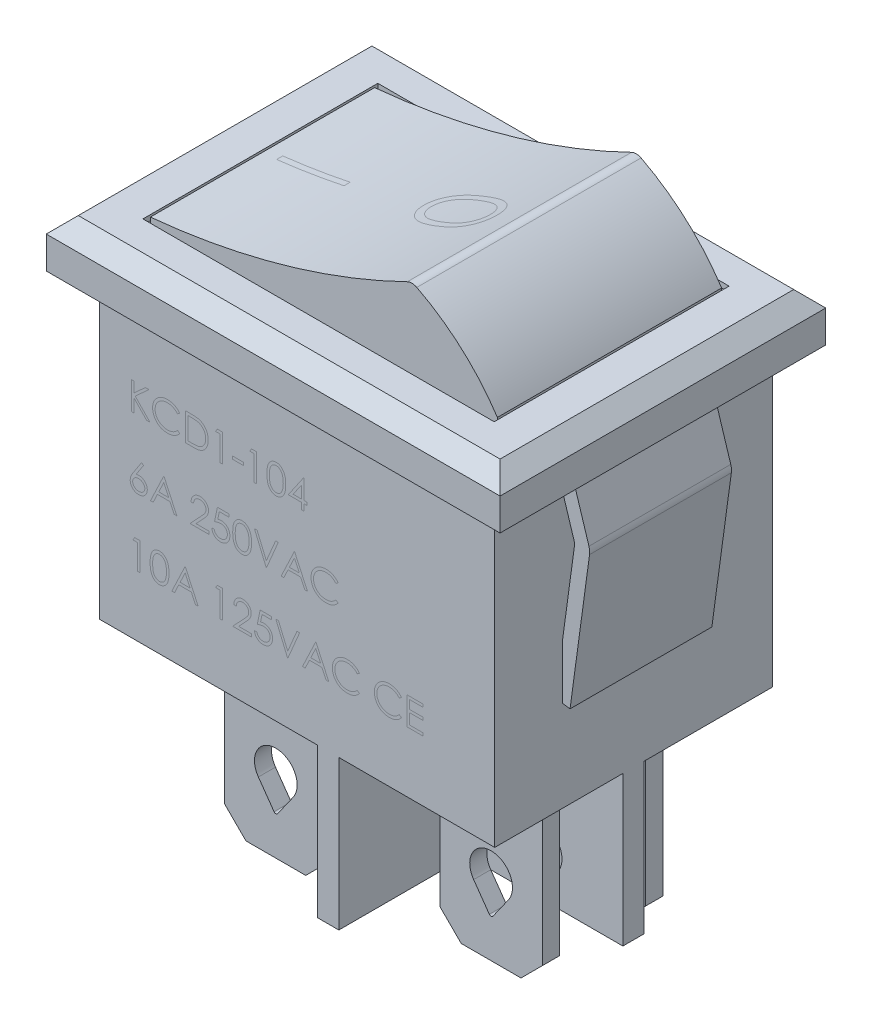
SolidWorks part; units mm, degrees
ref_plane "Front Plane" through (0, 0, 0) normal (0, 0, 1) x (1, 0, 0)
ref_plane "Top Plane" through (0, 0, 0) normal (0, 1, 0) x (1, 0, 0)
ref_plane "Right Plane" through (0, 0, 0) normal (1, 0, 0) x (0, 0, -1)
sketch "Sketch1" plane through (0, 0, 0) normal (0, 0, 1) x (1, 0, 0)
  line L1 (9.25, 7) -> (-9.25, 7)
  line L2 (9.25, 7) -> (9.25, -7)
  line L3 (9.25, -7) -> (-9.25, -7)
  line L4 (-9.25, 7) -> (-9.25, -7)
  line L5 (9.25, 7) -> (-9.25, -7) construction
  line L6 (9.25, -7) -> (-9.25, 7) construction
  point P0 (0, 0)
  dimension "D1" = 14
  dimension "D2" = 18.5
extrude "Boss-Extrude1" add sketch "Sketch1" along normal mid plane 13
sketch "Sketch2" plane through (0, 7, 0) normal (0, 1, 0) x (1, 0, 0)
  line L1 (10.625, 7.625) -> (-10.625, 7.625)
  line L2 (10.625, 7.625) -> (10.625, -7.625)
  line L3 (10.625, -7.625) -> (-10.625, -7.625)
  line L4 (-10.625, 7.625) -> (-10.625, -7.625)
  line L5 (10.625, 7.625) -> (-10.625, -7.625) construction
  line L6 (10.625, -7.625) -> (-10.625, 7.625) construction
  point P0 (0, 0)
  dimension "D1" = 15.25
  dimension "D2" = 21.25
extrude "Boss-Extrude2" add sketch "Sketch2" along normal blind 2.25
chamfer "Chamfer1" distance 0.75 angle 45 4 edges at (0, 9.25, -7.625) (10.625, 9.25, 0) (0, 9.25, 7.625) (-10.625, 9.25, 0)
sketch "Sketch11" plane through (0, 9.25, 0) normal (0, 1, 0) x (1, 0, 0)
  line L0 (-10.625, -7.625) -> (-10.625, 7.625) construction
  line L1 (-8.225, -5.5) -> (8.225, -5.5)
  line L2 (-8.225, -5.5) -> (-8.225, 5.5)
  line L3 (-8.225, 5.5) -> (8.225, 5.5)
  line L4 (8.225, -5.5) -> (8.225, 5.5)
  line L5 (-8.225, -5.5) -> (8.225, 5.5) construction
  line L6 (-8.225, 5.5) -> (8.225, -5.5) construction
  point P0 (0, 0)
  dimension "D1" = 2.4
  dimension "D2" = 11
extrude "Cut-Extrude6" cut sketch "Sketch11" against normal blind 0.25
sketch "Sketch3" plane through (0, 0, 0) normal (0, 0, 1) x (1, 0, 0)
  line L0 (8.125, 9.25) -> (4.125, 12.75) construction
  line L1 (-9.875, 9.25) -> (9.875, 9.25) construction
  line L2 (10.625, 8.5) -> (10.625, 7) construction
  line L4 (-10.625, 8.5) -> (-10.625, 7) construction
  line L5 (-8.125, 9.25) -> (8.125, 9.25) construction
  line L6 (-8.125, 9.25) -> (8.125, 9.25) construction
  line L7 (-8.125, 9.25) -> (-8.125, 8.95)
  line L8 (-8.125, 8.95) -> (8.125, 8.95)
  line L9 (8.125, 9.25) -> (8.125, 8.95)
  arc A0 (-8.125, 9.25) -> (3.9043, 12.6413) centre (-11.4546, 44.0913) ccw
  arc A1 (4.3525, 12.6366) -> (8.125, 9.25) centre (-0.2233, 3.7449) cw
  arc A2 (3.9043, 12.6413) -> (4.3525, 12.6366) centre (4.1237, 12.192) cw
  point P6 (-8.125, 9.25)
  dimension "D4" = 35
  dimension "D5" = 6.5
  dimension "D6" = 10
  dimension "D7" = 0.5
  dimension "D1" = 2.5
  dimension "D2" = 3.5
  dimension "D3" = 2.5
  dimension "D8" = 0.3
extrude "Boss-Extrude3" add sketch "Sketch3" along normal mid plane 10.5
sketch "Sketch4" plane through (0, -7, 0) normal (0, -1, 0) x (-1, 0, 0)
  line L0 (-9.25, 6.5) -> (9.25, 6.5) construction
  line L1 (-1.95, 6.5) -> (-0.95, 6.5)
  line L2 (-1.95, 6.5) -> (-1.95, -6.5)
  line L3 (-1.95, -6.5) -> (-0.95, -6.5)
  line L4 (-0.95, 6.5) -> (-0.95, -6.5)
  line L5 (9.25, -6.5) -> (-9.25, -6.5) construction
  line L6 (-9.25, -6.5) -> (-9.25, 6.5) construction
  line L7 (-1.45, -6.5) -> (-1.45, 6.5) construction
  line L8 (-9.25, 0.5) -> (9.25, 0.5)
  line L9 (-9.25, 0.5) -> (-9.25, -0.5)
  line L10 (-9.25, -0.5) -> (9.25, -0.5)
  line L11 (9.25, 0.5) -> (9.25, -0.5)
  line L12 (-9.25, 0.5) -> (9.25, -0.5) construction
  line L13 (-9.25, -0.5) -> (9.25, 0.5) construction
  line L14 (9.25, -6.5) -> (9.25, 6.5) construction
  line L15 (0, 0) -> (4.2269, 0) construction
  line M5 (9.25, 6.5) -> (-9.25, 6.5)
  line M6 (-9.25, 6.5) -> (-9.25, -6.5)
  line M7 (-9.25, -6.5) -> (9.25, -6.5)
  line M8 (9.25, -6.5) -> (9.25, 6.5)
  dimension "D1" = 8.3
  dimension "D2" = 1
extrude "Boss-Extrude4" add sketch "Sketch4" along normal blind 7 contours L10 L2 L8 M6 | L4 L10 L8 M8 | L2 L10 L4 L8 | L2 L8 L4 M5 | L10 L2 L4 M7 region at (1.45, -7, -3.5) region at (1.45, -7, 0) region at (5.6, -7, 0) region at (-4.15, -7, 0) region at (1.45, -7, 3.5)
sketch "Sketch5" plane through (0, -7, 0) normal (0, -1, 0) x (1, 0, 0)
  line L0 (1.95, 6.5) -> (9.25, 6.5) construction
  line L1 (3, 2.82) -> (7.8, 2.82)
  line L2 (3, 2.82) -> (3, 2.02)
  line L3 (3, 2.02) -> (7.8, 2.02)
  line L4 (7.8, 2.82) -> (7.8, 2.02)
  line L5 (3, 2.82) -> (7.8, 2.02) construction
  line L6 (3, 2.02) -> (7.8, 2.82) construction
  line L7 (-6.2, -2.9) -> (-1.4, -2.9)
  line L8 (-6.2, -2.9) -> (-6.2, -3.7)
  line L9 (-6.2, -3.7) -> (-1.4, -3.7)
  line L10 (-1.4, -2.9) -> (-1.4, -3.7)
  line L11 (-6.2, -2.9) -> (-1.4, -3.7) construction
  line L12 (-6.2, -3.7) -> (-1.4, -2.9) construction
  line L13 (-9.25, -6.5) -> (0.95, -6.5) construction
  line L14 (9.25, 6.5) -> (9.25, -6.5) construction
  line L15 (0, 0) -> (-13.591, 0) construction
  line L16 (0, 0) -> (0, 9.8331) construction
  line L17 (3, -2.02) -> (7.8, -2.82) construction
  line L18 (3, -2.82) -> (7.8, -2.02) construction
  line L19 (7.8, -2.82) -> (7.8, -2.02)
  line L20 (3, -2.02) -> (7.8, -2.02)
  line L21 (3, -2.82) -> (3, -2.02)
  line L22 (3, -2.82) -> (7.8, -2.82)
  line L23 (-6.2, 3.7) -> (-1.4, 2.9) construction
  line L24 (-6.2, 2.9) -> (-1.4, 3.7) construction
  line L25 (-1.4, 2.9) -> (-1.4, 3.7)
  line L26 (-6.2, 3.7) -> (-1.4, 3.7)
  line L27 (-6.2, 2.9) -> (-6.2, 3.7)
  line L28 (-6.2, 2.9) -> (-1.4, 2.9)
  point P0 (5.4, 2.42)
  point P5 (-3.8, -3.3)
  point P24 (5.4, -2.42)
  point P29 (-3.8, 3.3)
  dimension "D1" = 4.8
  dimension "D2" = 0.8
  dimension "D3" = 14
  dimension "D4" = 3.68
  dimension "D5" = 2.8
  dimension "D6" = 1.45
extrude "Boss-Extrude5" add sketch "Sketch5" along normal blind 8.36
chamfer "Chamfer2" distance 1 angle 45 8 edges at (7.8, -15.36, 2.42) (3, -15.36, 2.42) (-1.4, -15.36, -3.3) (-6.2, -15.36, -3.3) (7.8, -15.36, -2.42) (3, -15.36, -2.42) (-1.4, -15.36, 3.3) (-6.2, -15.36, 3.3)
sketch "Sketch6" plane through (0, 0, 2.82) normal (0, 0, 1) x (1, 0, 0)
  line L0 (6.8, -15.36) -> (4, -15.36) construction
  line L1 (5.3183, -13.5177) -> (4.5832, -12.4769)
  line L2 (5.4, -11.9) -> (5.4, -15.36) construction
  line L3 (-1.4, -10.68) -> (3, -10.68) construction
  line L4 (5.4817, -13.5177) -> (6.2168, -12.4769)
  line L5 (-1.4, -14.36) -> (-1.4, -7) construction
  line L6 (3, -14.36) -> (3, -7) construction
  line L7 (0.8, -10.68) -> (0.8, -14.52) construction
  line L9 (-3.8817, -13.5177) -> (-4.6168, -12.4769)
  line L10 (-3.7183, -13.5177) -> (-2.9832, -12.4769)
  arc A0 (6.2168, -12.4769) -> (4.5832, -12.4769) centre (5.4, -11.9) ccw
  arc A1 (5.4817, -13.5177) -> (5.3183, -13.5177) centre (5.4, -13.46) cw
  arc A2 (-3.8817, -13.5177) -> (-3.7183, -13.5177) centre (-3.8, -13.46) ccw
  arc A3 (-4.6168, -12.4769) -> (-2.9832, -12.4769) centre (-3.8, -11.9) cw
  dimension "D1" = 0.1
  dimension "D2" = 2.66
  dimension "D3" = 1
  dimension "D4" = 1.8
extrude "Cut-Extrude1" cut sketch "Sketch6" against normal through all and the other way through all
ref_plane "Plane2" through (-3.0139, 10.6909, 0) normal (0.2713, -0.9625, 0) x (-0.9625, -0.2713, 0)
sketch "Sketch7" plane through (-3.0139, 10.6909, 0) normal (0.2713, -0.9625, 0) x (-0.9625, -0.2713, 0)
  text T0 "<r90>I</r>" font "Century Gothic" height 3.2
  text T1 "<r90>0</r>"
wrap "Wrap1" sketch "Sketch7" wrap type scribe source sketch "Sketch7" face at (-2.034, 10.675, 0)
sketch "Sketch8" plane through (0, 0, 6.5) normal (0, 0, 1) x (1, 0, 0)
  text T0 "KCD1-104\r\n6A 250VAC\r\n10A 125VAC CE" font "Century Gothic" height 1.3
wrap "Wrap2" sketch "Sketch8" wrap type scribe source sketch "Sketch8" face at (-0.3688, -6.125, 6.5)
sketch "Sketch9" plane through (0, 0, 0) normal (0, 0, 1) x (1, 0, 0)
  line L0 (-9.25, 7) -> (-10.175, 4.05)
  line L1 (-10.175, 4.05) -> (-9.25, -2.75)
  line L2 (-9.25, 7) -> (-9.25, -7) construction
  line L3 (9.25, 7) -> (10.175, 4.05)
  line L4 (10.175, 4.05) -> (9.25, -2.75)
  line L5 (9.25, -7) -> (9.25, 7) construction
  line L6 (-10.625, 7) -> (10.625, 7) construction
  dimension "D1" = 2.95
  dimension "D2" = 6.8
  dimension "D3" = 20.35
extrude "Extrude-Thin14" add sketch "Sketch9" against normal mid plane 6.64 separate body thin thin type mid plane wall 0.7
sketch "Sketch10" plane through (0, 0, 3.32) normal (0, 0, 1) x (1, 0, 0)
  line L2 (-9.25, -7) -> (9.25, -7)
  line L3 (-9.25, -7) -> (-9.25, 7)
  line L4 (-9.25, 7) -> (9.25, 7)
  line L5 (9.25, -7) -> (9.25, 7)
extrude "Cut-Extrude5" cut sketch "Sketch10" against normal through all
